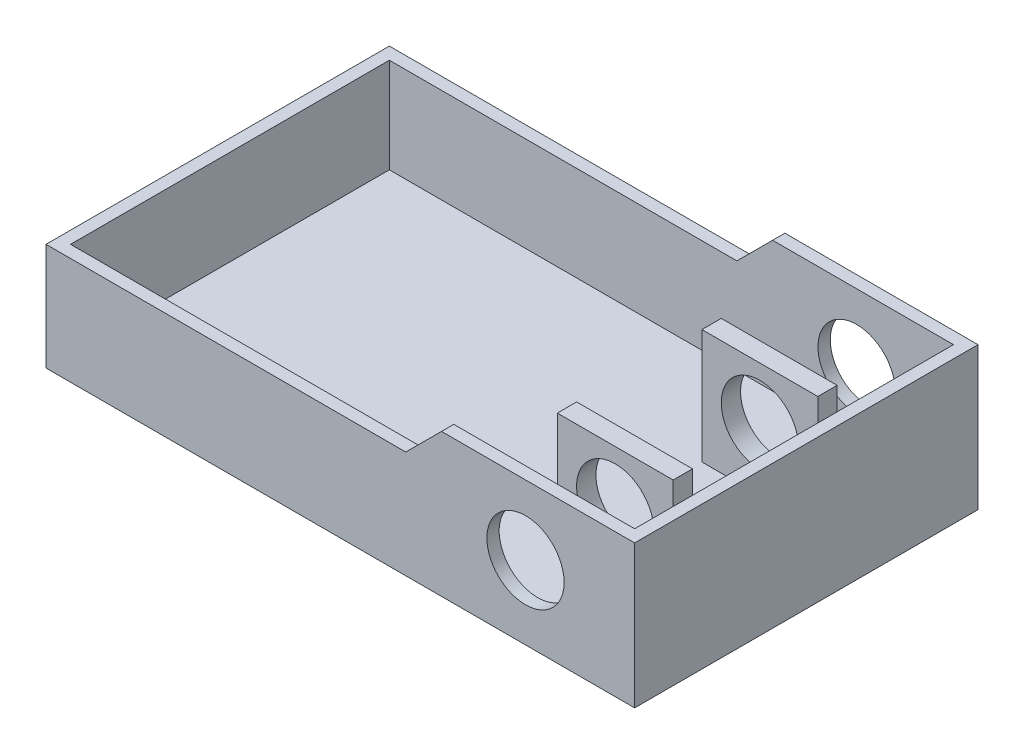
SolidWorks part; units mm, degrees
ref_plane "Front Plane" through (0, 0, 0) normal (0, 0, 1) x (1, 0, 0)
ref_plane "Top Plane" through (0, 0, 0) normal (0, 1, 0) x (1, 0, 0)
ref_plane "Right Plane" through (0, 0, 0) normal (1, 0, 0) x (0, 0, -1)
sketch "Sketch1" plane through (0, 0, 0) normal (0, 0, 1) x (1, 0, 0)
  line L1 (-152.4, 37) -> (152.4, 37)
  line L2 (-152.4, 37) -> (-152.4, -37)
  line L3 (-152.4, -37) -> (152.4, -37)
  line L4 (152.4, 37) -> (152.4, -37)
  line L5 (-152.4, 37) -> (152.4, -37) construction
  line L6 (-152.4, -37) -> (152.4, 37) construction
  point P0 (0, 0)
  dimension "D1" = 74
  dimension "D2" = 304.8
extrude "Boss-Extrude1" add sketch "Sketch1" along normal blind 177.8
shell "Shell1" thickness 6.35 removed face at (0, 37, 88.9)
sketch "Sketch2" plane through (0, 0, 177.8) normal (0, 0, 1) x (1, 0, 0)
  line L0 (-152.4, -37) -> (152.4, -37) construction
  line L1 (152.4, -37) -> (152.4, 37) construction
  circle A0 centre (95.9, 1) radius 20
  dimension "D1" = 38
  dimension "D2" = 56.5
  dimension "D3" = 40
extrude "Cut-Extrude1" cut sketch "Sketch2" against normal blind 200
sketch "Sketch3" plane through (0, 0, 177.8) normal (0, 0, 1) x (1, 0, 0)
  line L0 (125.9, 28.75) -> (65.9, 28.75)
  line L1 (65.9, 28.75) -> (65.9, -37)
  line L2 (-152.4, -37) -> (152.4, -37) construction
  line L3 (95.9, 28.75) -> (95.9, -37) construction
  line L4 (125.9, 28.75) -> (125.9, -37)
  line L5 (65.9, -37) -> (125.9, -37)
  circle A0 centre (95.9, 1) radius 20
  dimension "D1" = 30
  dimension "D2" = 65.75
extrude "Boss-Extrude2" add sketch "Sketch3" along normal blind 10 from offset 56.45 offset against normal yes
sketch "Sketch4" plane through (0, -30.65, 0) normal (0, 1, 0) x (1, 0, 0)
  line L0 (146.05, -88.9) -> (-146.05, -88.9) construction
  line L1 (146.05, -171.45) -> (146.05, -6.35) construction
  line L2 (-146.05, -171.45) -> (-146.05, -6.35) construction
ref_plane "Plane1" through (0, 0, 88.9) normal (0, 0, -1) x (-1, 0, 0)
mirror "Mirror1" about plane through (0, 0, 88.9) normal (0, 0, -1) of "Boss-Extrude2"
sketch "Sketch5" plane through (0, 0, 177.8) normal (0, 0, 1) x (1, 0, 0)
  line L0 (52.4, 37) -> (33.9, 18.5)
  line L1 (152.4, 37) -> (-152.4, 37) construction
  line L2 (33.9, 18.5) -> (-152.4, 18.5)
  line L3 (-152.4, 37) -> (-152.4, -37) construction
  line L4 (52.4, 37) -> (-152.4, 37)
  line L5 (-152.4, 37) -> (-152.4, 18.5)
  line L6 (152.4, -37) -> (152.4, 37) construction
  dimension "D1" = 45
  dimension "D2" = 18.5
  dimension "D3" = 100
extrude "Cut-Extrude2" cut sketch "Sketch5" against normal through all
